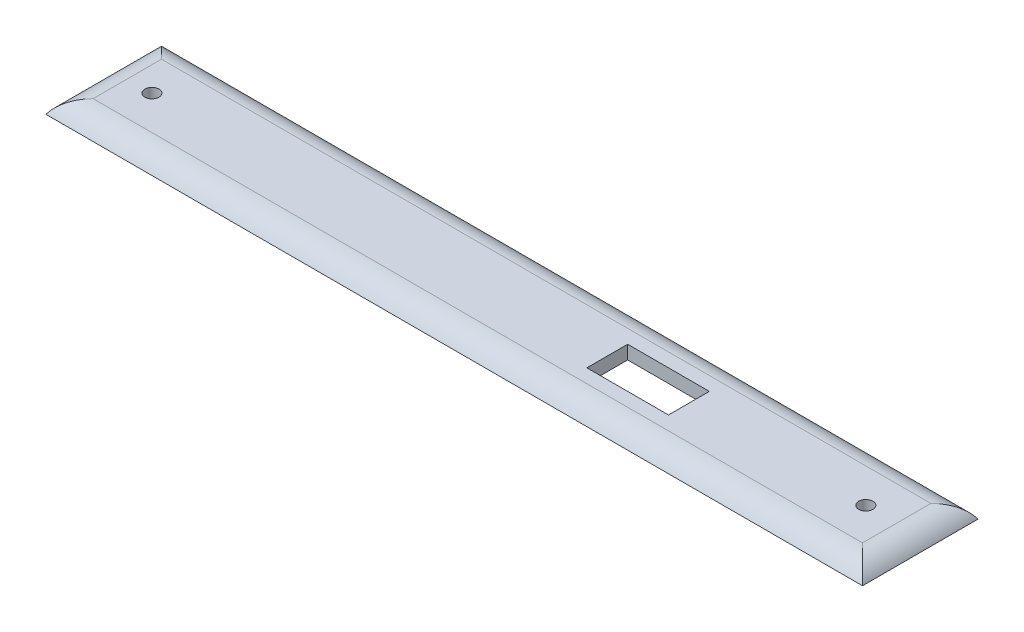
SolidWorks part; units mm, degrees
ref_plane "前视基准面" through (0, 0, 0) normal (0, 0, 1) x (1, 0, 0)
ref_plane "上视基准面" through (0, 0, 0) normal (0, 1, 0) x (1, 0, 0)
ref_plane "右视基准面" through (0, 0, 0) normal (1, 0, 0) x (0, 0, -1)
other "Configuration Table"
sketch "草图1" plane through (0, 0, 0) normal (0, 1, 0) x (1, 0, 0)
  line L1 (-129, 21.215) -> (129, 21.215)
  line L2 (-129, 21.215) -> (-129, -21.215)
  line L3 (-129, -21.215) -> (129, -21.215)
  line L4 (129, 21.215) -> (129, -21.215)
  line L5 (0, -21.215) -> (0, 21.215) construction
  line L6 (-129, 0) -> (129, 0) construction
  line L7 (-150, 21.215) -> (150, 21.215)
  line L8 (-150, 21.215) -> (-150, -21.215)
  line L9 (-150, -21.215) -> (150, -21.215)
  line L10 (150, 21.215) -> (150, -21.215)
  line L11 (0, -21.215) -> (0, 21.215) construction
  line L12 (-150, 0) -> (150, 0) construction
  circle A2 centre (-132.3, 0) radius 2.6
  circle A3 centre (130, 0) radius 2.6
  point P0 (0, 0)
  point P4 (0, 0)
  dimension "D4" = 5.2
  dimension "D5" = 5.2
  dimension "D6" = 17.7
  dimension "D7" = 20
  dimension "D1" = 258
  dimension "D2" = 42.43
  dimension "D3" = 300
extrude "凸台-拉伸1" add sketch "草图1" along normal blind 5 contours L2 L7 L8 L9 | L2 L3 L4 L1 | L4 L9 L10 L7 region at (-0.0651, 0, 0) region at (-139.6758, 0, 0) region at (139.6597, 0, 0)
fillet "圆角1" radius 10 4 edges at (150, 5, 0) (0, 5, 21.215) (-150, 5, 0) (0, 5, -21.215)
sketch "草图3" plane through (0, 5, 0) normal (0, 1, 0) x (1, 0, 0)
  line L0 (35, 0) -> (65, 0)
  line L2 (35, -7.5) -> (65, -7.5)
  line L3 (35, -7.5) -> (35, 7.5)
  line L4 (35, 7.5) -> (65, 7.5)
  line L5 (65, -7.5) -> (65, 7.5)
  line L6 (50, 7.5) -> (50, -7.5) construction
  line L7 (35, 0) -> (65, 0) construction
  line L9 (150, 21.215) -> (150, -21.215) construction
  point P4 (50, 0)
  dimension "D1" = 30
  dimension "D2" = 15
  dimension "D3" = 85
extrude "切除-拉伸2" cut sketch "草图3" against normal blind 5 contours L0 L5 L4 L3 | L2 L5 L0 L3 region at (50, 5, -3.75) region at (50, 5, 3.75)
